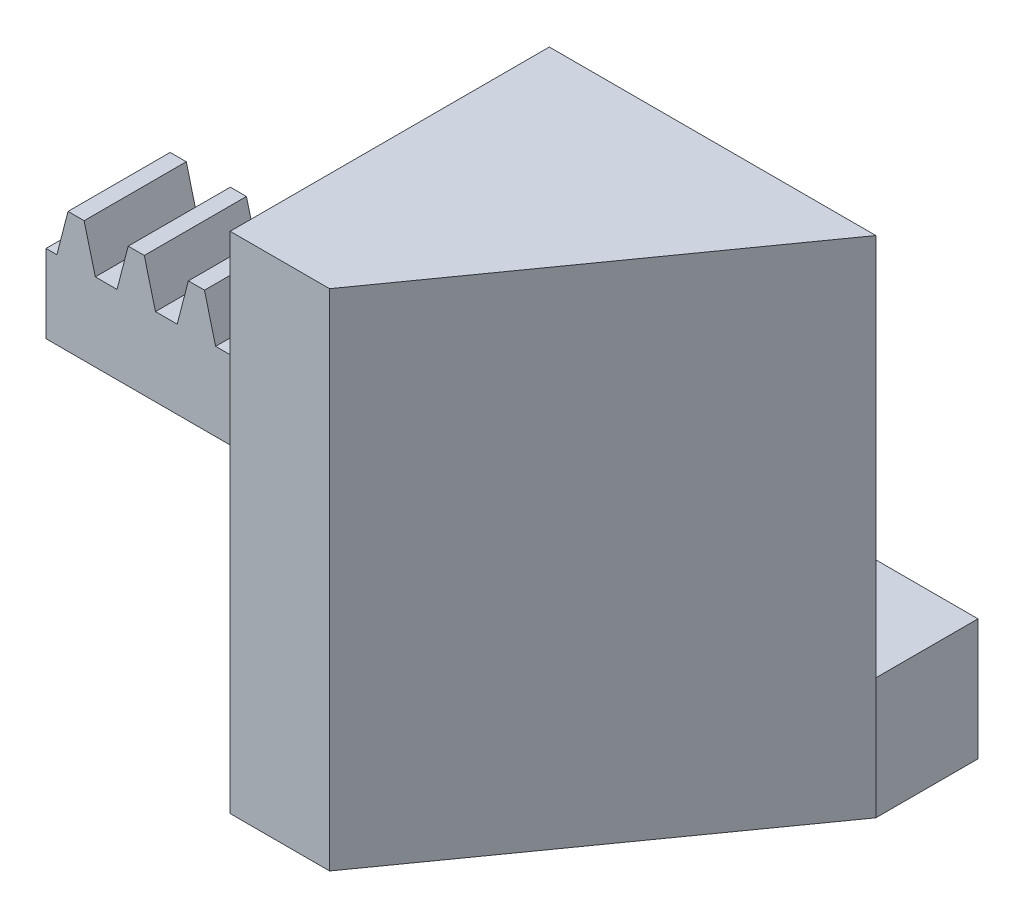
SolidWorks part; units mm, degrees
extrude "Blank" add sketch "BlankSke" against normal blind 8
sketch "BlankSke" plane through (0, 0, 0) normal (0, 0, 1) x (1, 0, 0)
  line L1 (0, 0) -> (50, 0)
  line L2 (0, 0) -> (0, 9.5)
  line L3 (0, 9.5) -> (50, 9.5)
  line L4 (50, 0) -> (50, 9.5)
  dimension "Length" = 50
ref_plane "Plane1" through (0, 0, 0) normal (0, 0, 1) x (1, 0, 0)
ref_plane "Plane2" through (0, 0, 0) normal (0, 1, 0) x (1, 0, 0)
ref_plane "Plane3" through (0, 0, 0) normal (1, 0, 0) x (0, 0, -1)
other "Configuration Table"
sketch "HoldingSke" plane through (0, 0, 0) normal (0, 1, 0) x (1, 0, 0)
  line L0 (0, 0) -> (0.0928, 0.6602)
  line L1 (-15, 0) -> (100, 0) construction
  line L2 (0, 0) -> (-2.1039, 2.3779)
  line L3 (0, 0) -> (-11.863, 4.5341)
  line L4 (0, 0) -> (8.4473, 1.7955)
  line L5 (0, 0) -> (-23.7986, -8.8762)
  line L6 (0, 0) -> (-10.5278, -7.1032)
  line L9 (-67.7845, 28.3722) -> (-19.3772, 40.8912)
  line L10 (-76.2, 3.8779) -> (-68.2, 3.8779)
  line L11 (0, 0) -> (-8, 0)
  line L12 (-76.2, 101.6) -> (-76.147, 101.6)
  line L13 (24.9733, 27.94) -> (52.9518, 28.4284)
  line L14 (24.9733, 27.94) -> (24.9743, 27.94)
  line L15 (24.9733, 27.94) -> (100.4006, 29.5858)
  circle A0 centre (0, 0) radius 19.05
  circle A1 centre (0, 0) radius 4
  circle A2 centre (0, 0) radius 12.7
  dimension "Num_teeth" = 12
  dimension "Width" = 8
  dimension "Length" = 50
  dimension "Pitch_height" = 8
sketch "TooCutSkeIll" plane through (0, 0, 0) normal (0, 0, 1) x (1, 0, 0)
  line L0 (-1.7134, 9.455) -> (-0.9251, 6.4069)
  line L1 (-0.5611, 6.125) -> (0.5611, 6.125)
  line L2 (0.9251, 6.4069) -> (1.7134, 9.455)
  line L3 (50, 9.5) -> (0, 9.5) construction
  line L4 (0, 0) -> (0, 64.897) construction
  line L5 (-13.208, 8) -> (12.954, 8) construction
  line L6 (0, 0) -> (50, 0) construction
  line L7 (1.3371, 8) -> (1.3371, 48.7463) construction
  line L8 (-1.3371, 8) -> (-1.3371, 48.7463) construction
  line L9 (1.7715, 9.5) -> (1.7715, 9.5254)
  line L10 (-1.7715, 9.5) -> (-1.7715, 9.5254)
  line L11 (-1.7715, 9.5254) -> (1.7715, 9.5254)
  arc A0 (0.5611, 6.125) -> (0.9251, 6.4069) centre (0.5611, 6.501) ccw
  arc A1 (-0.9251, 6.4069) -> (-0.5611, 6.125) centre (-0.5611, 6.501) ccw
  arc A2 (1.7715, 9.5) -> (1.7134, 9.455) centre (1.7715, 9.44) ccw
  arc A3 (-1.7134, 9.455) -> (-1.7715, 9.5) centre (-1.7715, 9.44) ccw
  dimension "Addendum_plus" = 1.5254
  dimension "Pitch_height" = 8
  dimension "Pressure_angle" = 14.5
  dimension "Gap_width" = 2.6742
  dimension "Dedendum" = 1.875
extrude "ToothCutIll" [suppressed] cut sketch "TooCutSkeIll" against normal through all
sketch "TooCutSkeSim" plane through (0, 0, 0) normal (0, 0, 1) x (1, 0, 0)
  line L0 (0.8522, 6.125) -> (-0.8522, 6.125)
  line L1 (1.7316, 9.5254) -> (0.8522, 6.125)
  line L2 (0, 17.4625) -> (0, 53.467) construction
  line L3 (1.7316, 9.5254) -> (-1.7316, 9.5254)
  line L6 (-1.7316, 9.5254) -> (-0.8522, 6.125)
  line L9 (-1.3371, 8) -> (1.3371, 8) construction
  line L10 (0, 0) -> (50, 0) construction
  line L11 (1.3371, 8) -> (1.3371, 53.467) construction
  line L12 (-1.3371, 8) -> (-1.3371, 53.467) construction
  dimension "Addendum_plus" = 1.5254
  dimension "Pitch_height" = 8
  dimension "Pressure_angle" = 14.5
  dimension "Gap_width" = 2.6742
  dimension "Dedendum" = 1.875
extrude "ToothCutSim" cut sketch "TooCutSkeSim" against normal through all
pattern_linear "TeethCuts" count 12 spacing 4.7124 along (1, 0, 0) of "ToothCutIll", "ToothCutSim"
sketch "Sketch3" plane through (50, 0, 0) normal (1, 0, 0) x (0, 0, -1)
  line L1 (0, 9.5) -> (8, 9.5)
  line L2 (0, 9.5) -> (0, 0)
  line L3 (0, 0) -> (8, 0)
  line L4 (8, 9.5) -> (8, 0)
extrude "Boss-Extrude2" add sketch "Sketch3" along normal blind 15
sketch "Sketch5" [suppressed] plane through (0, 9.5, 0) normal (0, 1, 0) x (1, 0, 0)
  line L1 (39.4241, 8) -> (55, 8)
  line L2 (39.4241, 8) -> (39.4241, 0)
  line L3 (39.4241, 0) -> (55, 0)
  line L4 (55, 8) -> (55, 0)
extrude "Boss-Extrude3" [suppressed] add sketch "Sketch5" along normal blind 30
sketch "Sketch7" plane through (0, 0, 0) normal (0, 1, 0) x (1, 0, 0)
  line L4 (65, 0) -> (39.4241, 0)
  line L5 (0, 0) -> (65, 0) construction
  line L9 (39.4241, 0) -> (39.4241, -25)
  line L10 (39.4241, -25) -> (47.2121, -25)
  line L11 (47.2121, -25) -> (65, 0)
extrude "Boss-Extrude5" add sketch "Sketch7" along normal blind 39.5
sketch "Sketch8" [suppressed] plane through (0, 0, -8) normal (0, 0, -1) x (-1, 0, 0)
  line L1 (-39.4241, 9.5) -> (-55, 9.5)
  line L2 (-39.4241, 9.5) -> (-39.4241, 39.5)
  line L3 (-39.4241, 39.5) -> (-55, 39.5)
  line L4 (-55, 9.5) -> (-55, 39.5)
extrude "Cut-Extrude1" [suppressed] cut sketch "Sketch8" against normal blind 11
equation "' \"Module@HoldingSke\" = 6.35"
equation "' \"Num_teeth@HoldingSke\" = 12"
equation "' \"Ap@HoldingSke\" =  20"
equation "' \"Ap@HoldingSke\" = 20"
equation "' \"Width@HoldingSke\" = 0.25 * 25.4"
equation "' \"Show_teeth@HoldingSke\" = 500"
equation "' \"Backlash@HoldingSke\" = 0.009 * 25.4"
equation "' \"Addendum_fac@HoldingSke\" = 1.0"
equation "' \"Dedendum_fac@HoldingSke\" = 1.25"
equation "' \"Dedendum_add@HoldingSke\" = 0.00005 * 25.4"
equation "' \"Clearance_fac@HoldingSke\" = 0.25"
equation "' \"Pitch_height@HoldingSke\" = 1 * 25.4"
equation "' \"Length@HoldingSke\" = 4.71 * 25.4"
equation "\"Pitch@HoldingSke\" = 1 / \"Module@HoldingSke\""
equation "\"MPH@HoldingSke\" = \"Dedendum_fac@HoldingSke\" / \"Pitch@HoldingSke\" + 2 * \"Dedendum_add@HoldingSke\" + 0.002 * 25.4"
equation "\"MPH@HoldingSke\" = ((sgn( \"MPH@HoldingSke\" - \"Pitch_height@HoldingSke\")+1)*( \"MPH@HoldingSke\" - \"Pitch_height@HoldingSke\"))/2 + \"Pitch_height@HoldingSke\""
equation "\"Blank_height@BlankSke\" = \"Pitch_height@HoldingSke\" + \"Addendum_fac@HoldingSke\"  / \"Pitch@HoldingSke\" "
equation "\"Length@BlankSke\" =  \"Length@HoldingSke\""
equation "\"Face_width@Blank\" = \"Width@HoldingSke\""
equation "\"Pressure_angle@TooCutSkeIll\" = \"Ap@HoldingSke\""
equation "\"Addendum_plus@TooCutSkeIll\" =  \"Addendum_fac@HoldingSke\"  / \"Pitch@HoldingSke\" + 0.001 *25.4"
equation "\"Dedendum@TooCutSkeIll\" = \"Dedendum_fac@HoldingSke\"  / \"Pitch@HoldingSke\""
equation "\"Pitch_height@TooCutSkeIll\" =  \"MPH@HoldingSke\""
equation "\"Gap_width@TooCutSkeIll\" = 3.14159265 / 2 / \"Pitch@HoldingSke\" + 6 * \"Backlash@HoldingSke\""
equation "\"Pressure_angle@TooCutSkeSim\" = \"Ap@HoldingSke\""
equation "\"Addendum_plus@TooCutSkeSim\" =  \"Addendum_fac@HoldingSke\"  / \"Pitch@HoldingSke\" + 0.001 * 25.4"
equation "\"Dedendum@TooCutSkeSim\" = \"Dedendum_fac@HoldingSke\"  / \"Pitch@HoldingSke\""
equation "\"Pitch_height@TooCutSkeSim\" =  \"MPH@HoldingSke\""
equation "\"Gap_width@TooCutSkeSim\" = 3.14159265 / 2 / \"Pitch@HoldingSke\" + 6 * \"Backlash@HoldingSke\""
equation "\"Root_fillet@TooCutSkeIll\" = \"Clearance_fac@HoldingSke\" / \"Pitch@HoldingSke\" + \"Dedendum_add@HoldingSke\""
equation "\"Break_rad@TooCutSkeIll\" = 0.02 / \"Pitch@HoldingSke\" * 2"
equation "\"Linear_pitch@TeethCuts\" = 3.14159265 / \"Pitch@HoldingSke\""
equation "\"Num_teeth@HoldingSke\" = int( ( \"Length@HoldingSke\" + 0 ) / (3.14159265 / \"Pitch@HoldingSke\")) + 0.9999  + 1"
equation " \"Num_teeth@TeethCuts\" = int( \"Show_teeth@HoldingSke\" ) + 1"
equation " \"Num_teeth@TeethCuts\" = ((sgn( \"Num_teeth@TeethCuts\" - \"Num_teeth@HoldingSke\" )-1)*( \"Num_teeth@TeethCuts\" - \"Num_teeth@HoldingSke\" ))/-2+ \"Num_teeth@HoldingSke\""
equation " \"Num_teeth@TeethCuts\" = ((sgn( \"Num_teeth@TeethCuts\" - 2.0)+1)*( \"Num_teeth@TeethCuts\" - 2.0))/2 +2.0"
